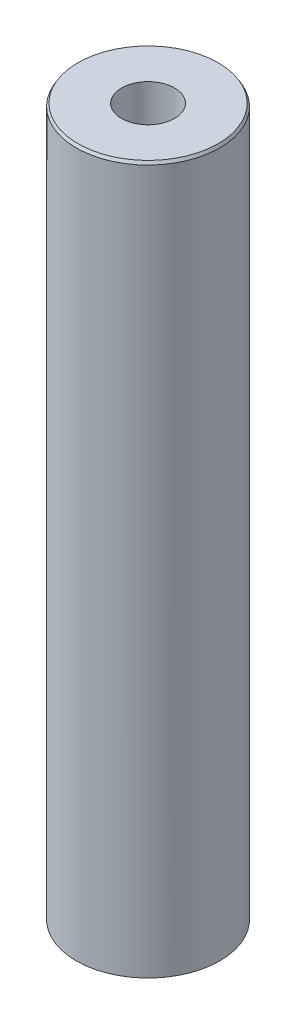
SolidWorks part; units mm, degrees
ref_plane "Front Plane" through (0, 0, 0) normal (0, 0, 1) x (1, 0, 0)
ref_plane "Top Plane" through (0, 0, 0) normal (0, 1, 0) x (1, 0, 0)
ref_plane "Right Plane" through (0, 0, 0) normal (1, 0, 0) x (0, 0, -1)
sketch "Sketch1" plane through (0, 0, 0) normal (0, 1, 0) x (1, 0, 0)
  circle A0 centre (0, 0) radius 22.5
  dimension "SHAFT_OD" = 45
extrude "Boss-Extrude1" add sketch "Sketch1" along normal blind 222.1383
sketch "Sketch2" plane through (0, 0, 0) normal (0, 1, 0) x (1, 0, 0)
  circle A0 centre (0, 0) radius 8.3002
  dimension "BORE_D" = 16.6004
extrude "Cut-Extrude1" cut sketch "Sketch2" along normal through all
chamfer "Chamfer1" distance 0.8933 angle 30 2 edges at (0, 222.1383, 22.5) (0, 0, 22.5) first distance on face at (0, 222.1383, 22.5) first distance on face at (0, 0, 8.3002)
